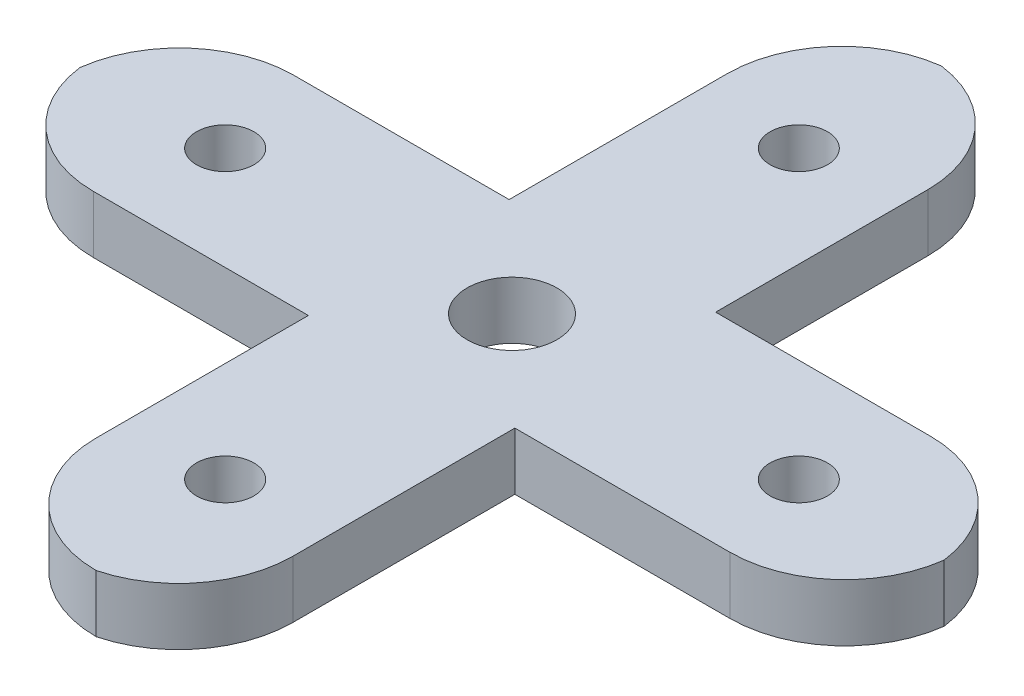
SolidWorks part; units mm, degrees
ref_plane "Front Plane" through (0, 0, 0) normal (0, 0, 1) x (1, 0, 0)
ref_plane "Top Plane" through (0, 0, 0) normal (0, 1, 0) x (1, 0, 0)
ref_plane "Right Plane" through (0, 0, 0) normal (1, 0, 0) x (0, 0, -1)
sketch "Sketch1" plane through (0, 0, 0) normal (0, 1, 0) x (1, 0, 0)
  line L0 (-4.2008, 17.9949) -> (-4.2008, 3.2629)
  line L1 (19.2942, -5.3731) -> (4.6892, -5.3731)
  line L2 (19.2942, -5.3731) -> (19.2942, 3.5169)
  line L3 (19.2942, 3.5169) -> (4.6892, 3.5169)
  line L4 (4.6892, 3.5169) -> (4.6892, 17.9949)
  line L5 (19.2942, -5.3731) -> (4.6892, 3.5169) construction
  line L6 (19.2942, 3.5169) -> (4.6892, -5.3731) construction
  line L7 (-4.2008, -20.1051) -> (4.6892, -20.1051)
  line L8 (-4.2008, -5.6271) -> (-4.2008, -20.1051)
  line L9 (-4.2008, 17.9949) -> (4.6892, 17.9949)
  line L10 (4.6892, -5.3731) -> (4.6892, -20.1051)
  line L11 (-4.2008, -20.1051) -> (4.6892, 17.9949) construction
  line L12 (-4.2008, 17.9949) -> (4.6892, -20.1051) construction
  line L13 (-18.8058, -5.6271) -> (-4.2008, -5.6271)
  line L14 (-18.8058, -5.6271) -> (-18.8058, 3.2629)
  line L15 (-18.8058, 3.2629) -> (-4.2008, 3.2629)
  line L17 (-18.8058, -5.6271) -> (-4.2008, 3.2629) construction
  line L18 (-18.8058, 3.2629) -> (-4.2008, -5.6271) construction
  point P0 (0, 0)
  point P1 (11.9917, -0.9281)
  point P6 (0.2442, -1.0551)
  point P12 (-11.5033, -1.1821)
  dimension "D1" = 38.1
  dimension "D2" = 8.89
  dimension "D3" = 8.89
  dimension "D4" = 14.605
  dimension "D5" = 14.605
  dimension "D6" = 8.89
  dimension "D7" = 14.732
  dimension "D8" = 14.732
extrude "Boss-Extrude1" add sketch "Sketch1" along normal blind 2.54
fillet "Fillet1" radius 5.08 1 edges at (-4.2008, 1.27, 20.1051)
fillet "Fillet2" radius 5.08 7 edges at (-4.2008, 1.27, -17.9949) (-18.8058, 1.27, -3.2629) (-18.8058, 1.27, 5.6271) (4.6892, 1.27, -17.9949) (19.2942, 1.27, -3.5169) (19.2942, 1.27, 5.3731) (4.6892, 1.27, 20.1051)
sketch "Sketch2" plane through (0, 2.54, 0) normal (0, 1, 0) x (1, 0, 0)
  line L0 (0.2442, -1.0551) -> (0.2442, 17.9551) construction
  circle A0 centre (0.2442, -1.0551) radius 1.9895
  circle A1 centre (0.2442, 11.6449) radius 1.27
  circle A2 centre (0.2442, -13.7551) radius 1.27
  circle A3 centre (-12.4558, -1.0551) radius 1.27
  circle A4 centre (12.9442, -1.0551) radius 1.27
  dimension "D1" = 12.7
  dimension "D2" = 12.7
  dimension "D3" = 12.7
  dimension "D4" = 12.7
extrude "Cut-Extrude1" cut sketch "Sketch2" against normal blind 2.54
